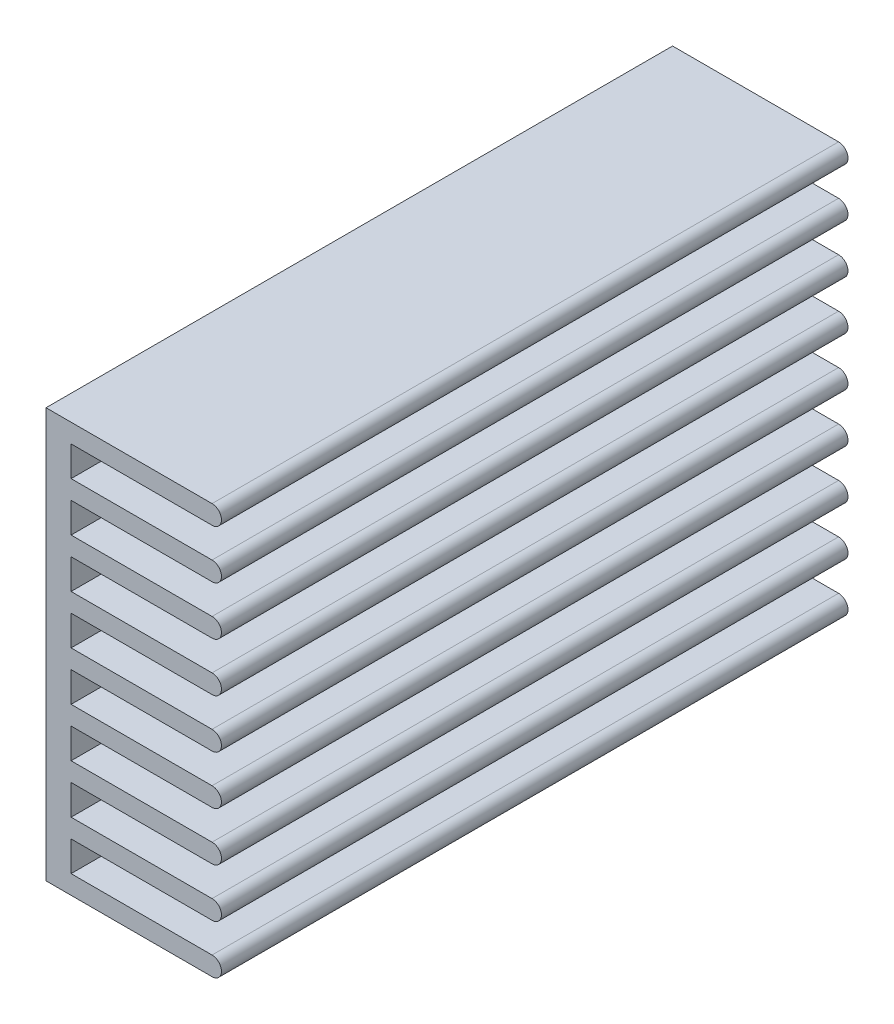
SolidWorks part; units mm, degrees
material "Stop 1060"
ref_plane "Front" through (0, 0, 0) normal (0, 0, 1) x (1, 0, 0)
ref_plane "Top" through (0, 0, 0) normal (0, 1, 0) x (1, 0, 0)
ref_plane "Right" through (0, 0, 0) normal (1, 0, 0) x (0, 0, -1)
sketch "Szkic1" plane through (0, 0, 0) normal (0, 0, 1) x (1, 0, 0)
  line L0 (13.25, 1.5) -> (2, 1.5)
  line L1 (0, 0) -> (13.25, 0)
  line L2 (0, 0) -> (0, 32.7)
  line L5 (13.25, 5.4) -> (2, 5.4)
  line L6 (2, 3.9) -> (13.25, 3.9)
  line L7 (13.25, 9.3) -> (2, 9.3)
  line L8 (2, 7.8) -> (13.25, 7.8)
  line L9 (13.25, 13.2) -> (2, 13.2)
  line L10 (2, 11.7) -> (13.25, 11.7)
  line L11 (13.25, 17.1) -> (2, 17.1)
  line L12 (2, 15.6) -> (13.25, 15.6)
  line L13 (13.25, 21) -> (2, 21)
  line L14 (2, 19.5) -> (13.25, 19.5)
  line L15 (13.25, 24.9) -> (2, 24.9)
  line L16 (2, 23.4) -> (13.25, 23.4)
  line L17 (13.25, 28.8) -> (2, 28.8)
  line L18 (2, 27.3) -> (13.25, 27.3)
  line L19 (13.25, 32.7) -> (0, 32.7)
  line L20 (2, 31.2) -> (13.25, 31.2)
  line L21 (2, 31.2) -> (2, 28.8)
  line L22 (2, 3.9) -> (2, 1.5)
  line L23 (2, 7.8) -> (2, 5.4)
  line L24 (2, 11.7) -> (2, 9.3)
  line L25 (2, 15.6) -> (2, 13.2)
  line L26 (2, 19.5) -> (2, 17.1)
  line L27 (2, 23.4) -> (2, 21)
  line L28 (2, 27.3) -> (2, 24.9)
  arc A0 (13.25, 0) -> (13.25, 1.5) centre (13.25, 0.75) ccw
  arc A1 (13.25, 3.9) -> (13.25, 5.4) centre (13.25, 4.65) ccw
  arc A2 (13.25, 7.8) -> (13.25, 9.3) centre (13.25, 8.55) ccw
  arc A3 (13.25, 11.7) -> (13.25, 13.2) centre (13.25, 12.45) ccw
  arc A4 (13.25, 15.6) -> (13.25, 17.1) centre (13.25, 16.35) ccw
  arc A5 (13.25, 19.5) -> (13.25, 21) centre (13.25, 20.25) ccw
  arc A6 (13.25, 23.4) -> (13.25, 24.9) centre (13.25, 24.15) ccw
  arc A7 (13.25, 27.3) -> (13.25, 28.8) centre (13.25, 28.05) ccw
  arc A8 (13.25, 31.2) -> (13.25, 32.7) centre (13.25, 31.95) ccw
  dimension "D4" = 2
  dimension "D2" = 1.5
  dimension "D3" = 9
extrude "Dodanie-wyciągnięcie1" add sketch "Szkic1" along normal blind 50
